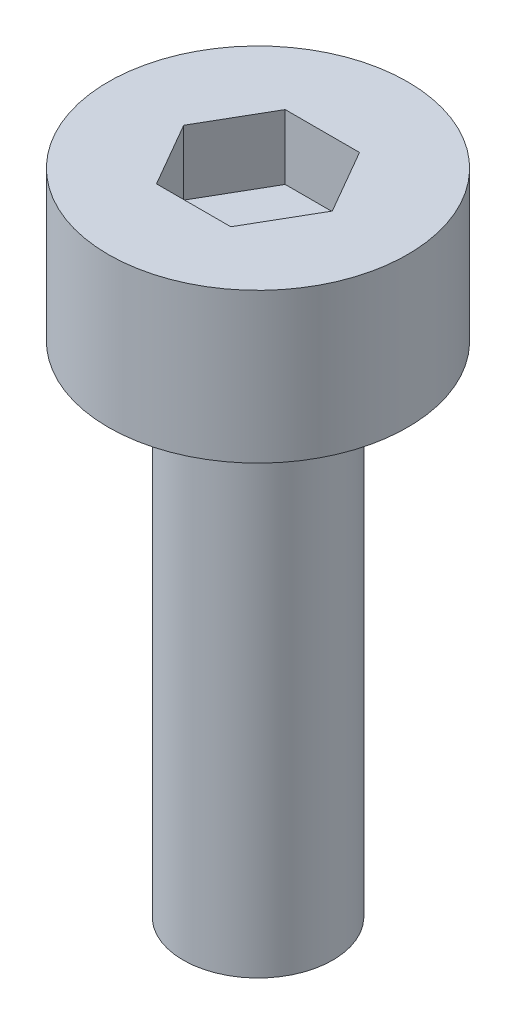
SolidWorks part; units mm, degrees
ref_plane "Front Plane" through (0, 0, 0) normal (0, 0, 1) x (1, 0, 0)
ref_plane "Top Plane" through (0, 0, 0) normal (0, 1, 0) x (1, 0, 0)
ref_plane "Right Plane" through (0, 0, 0) normal (1, 0, 0) x (0, 0, -1)
sketch "Sketch1" plane through (0, 0, 0) normal (0, 1, 0) x (1, 0, 0)
  circle A0 centre (0, 0) radius 1.5
  dimension "D1" = 3
extrude "ScrewShaft" add sketch "Sketch1" along normal blind 10
sketch "Sketch2" plane through (0, 10, 0) normal (0, 1, 0) x (1, 0, 0)
  circle A0 centre (0, 0) radius 3
  dimension "D1" = 6
extrude "Boss-Extrude2" add sketch "Sketch2" along normal blind 3
sketch "Sketch3" plane through (0, 13, 0) normal (0, 1, 0) x (1, 0, 0)
  line L0 (0, 0) -> (0, 1.29) construction
  line L1 (1.4896, 0) -> (0.7448, 1.29)
  line L2 (0.7448, 1.29) -> (-0.7448, 1.29)
  line L3 (-0.7448, 1.29) -> (-1.4896, 0)
  line L4 (-1.4896, 0) -> (-0.7448, -1.29)
  line L5 (-0.7448, -1.29) -> (0.7448, -1.29)
  line L6 (0.7448, -1.29) -> (1.4896, 0)
  circle A0 centre (0, 0) radius 1.29 construction
  dimension "D1" = 2.58
extrude "Cut-Extrude1" cut sketch "Sketch3" against normal blind 1.3
equation "\"X-ROD-SPACING\"=45"
equation "\"Y-ROD-SPACING\"=75"
equation "\"Z-ROD-SPACING\"=17.5"
equation "\"Y-BED-OFFSET\"=2"
equation "\"Y-BED-ROD-INSET\"=3.5"
equation "\"T-SLOT-NUT-FILLET-RADIUS\"=0.5"
equation "\"T-SLOT-SCREW-SHAFT-RADIUS\"=1.55"
equation "\"T-SLOT-SCREW-SHAFT-CUTOUT-LENGTH\"=11"
equation "\"T-SLOT-NUT-DEPTH\"=3.5"
equation "\"T-SLOT-NUT-WIDTH\"=2.85"
equation "\"T-SLOT-NUT-END-DISTANCE\"=8"
equation "\"ACRYLIC-THICKNESS\"=10"
equation "\"ACRYLIC-THICKNESS2\"=4.5"
equation "\"ACRYLIC-TAB-CUTOUT-SIZE\"=\"ACRYLIC-THICKNESS\"+\"ACRYLIC-TAB-TOLERANCE\"*2"
equation "\"ACRYLIC-TAB-WIDTH\"=\"ACRYLIC-THICKNESS\""
equation "\"ACRYLIC-M3-HOLE\"=2.9"
equation "\"SMOOTHROD-CAP-SCREW-DISTANCE\"=20"
equation "\"FRAME-WIDTH-INNER\"=370"
equation "\"NEMA17-HOLE-SPACING\"=31"
equation "\"NEMA17-CENTRAL-CUTOUT\"=22.5"
equation "\"Z-BRACKET-REACH\"=55"
equation "\"TOP-BRACKET-SPACING\"=40"
equation "\"SMOOTHROD-X-LENGTH\"=350"
equation "\"SMOOTHROD-Y-LENGTH\"=350"
equation "\"SMOOTHROD-Z-LENGTH\"=350"
equation "\"SMOOTHROD-TIGHTENING-HEADROOM\"=.25"
equation "\"LEADSCREW-Z-LENGTH\"=300"
equation "\"SCREW-LENGTH-FRAME\"=\"ACRYLIC-THICKNESS\" + 10"
equation "\"SCREW-HEAD-RADIUS\"=6"
equation "\"PRINTED-X-SMOOTHROD-DIAMETER\"=8.8"
equation "\"PRINTED-X-SMOOTHROD-CUTOUT\"=10"
equation "\"PRINTED-X-BASE-HEIGHT\"=10"
equation "\"PRINTED-LM8UU-CUTOUT-SIZE\"=15.5"
equation "\"PRINTED-LM8UU-CUTOUT-LENGTH\"=24.5"
equation "\"PRINTED-X-IDLER-HEIGHT\"=16"
equation "\"PSU-MOUNTING-WIDTH\"=95"
equation "\"PSU-MOUNTING-HEIGHT\"=177"
equation "\"D1@Sketch2\"=\"SCREW-HEAD-RADIUS\""
